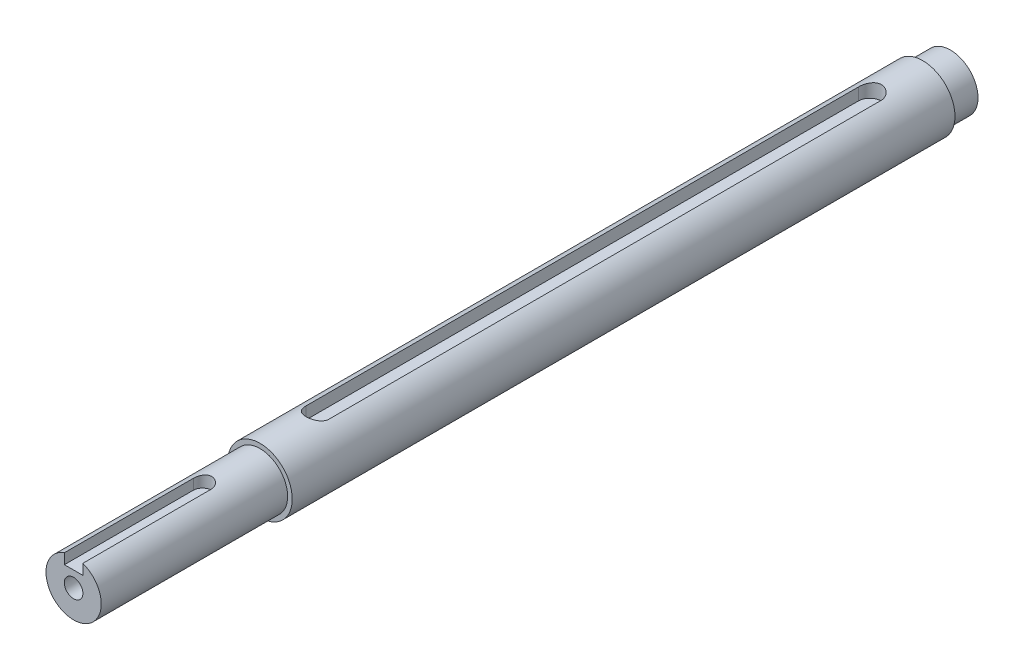
SolidWorks part; units mm, degrees
ref_plane "Front Plane" through (0, 0, 0) normal (0, 0, 1) x (1, 0, 0)
ref_plane "Top Plane" through (0, 0, 0) normal (0, 1, 0) x (1, 0, 0)
ref_plane "Right Plane" through (0, 0, 0) normal (1, 0, 0) x (0, 0, -1)
sketch "Sketch1" plane through (0, 0, 0) normal (1, 0, 0) x (0, 0, -1)
  line L0 (0, 0) -> (183, 0) construction
  line L1 (183, 0) -> (183, 6)
  line L3 (-7.5, 6) -> (-7.5, 0)
  line L5 (-7.5, 6) -> (33, 6)
  line L6 (33, 6) -> (33, 7)
  line L7 (33, 7) -> (177, 7)
  line L8 (-8, 5.9618) -> (-8, -6) construction
  line L9 (33, -12) -> (33, 12) construction
  line L10 (33, -50) -> (33, 50) construction
  line L11 (177, 7) -> (177, 6)
  line L12 (177, 6) -> (183, 6)
  line L13 (183, 0) -> (-7.5, 0)
  dimension "D1" = 12
  dimension "D2" = 0.5
  dimension "D3" = 14
  dimension "D4" = 150
  dimension "D5" = 12
  dimension "D6" = 6
revolve "Revolve1" add sketch "Sketch1" angle 360 about L0
sketch "Sketch2" plane through (0, 0, 7.5) normal (0, 0, 1) x (1, 0, 0)
  circle A0 centre (0, 0) radius 2.0193
  dimension "D1" = 4.0386
extrude "Cut-Extrude1" cut sketch "Sketch2" against normal blind 25
sketch "Sketch3" plane through (0, 0, -183) normal (0, 0, -1) x (-1, 0, 0)
  line L1 (-2.5, 8.9) -> (2.5, 8.9)
  line L2 (-2.5, 8.9) -> (-2.5, 3.9)
  line L3 (-2.5, 3.9) -> (2.5, 3.9)
  line L4 (2.5, 8.9) -> (2.5, 3.9)
  circle A1 centre (0, 0) radius 7 construction
  point P4 (0, 3.9)
  dimension "D1" = 5
  dimension "D2" = 3.1
extrude "Cut-Extrude2" cut sketch "Sketch3" against normal offset from surface (125 mm away) 10 from offset 15 contours L1 L4 L3 L2 up to face at (6, 0, -33) offset against normal yes
sketch "Sketch4" plane through (0, 0, 7.5) normal (0, 0, 1) x (1, 0, 0)
  line L1 (-2, 3.4) -> (2, 3.4)
  line L2 (-2, 3.4) -> (-2, 7.4)
  line L3 (-2, 7.4) -> (2, 7.4)
  line L4 (2, 3.4) -> (2, 7.4)
  line L5 (-2, 3.4) -> (2, 7.4) construction
  line L6 (-2, 7.4) -> (2, 3.4) construction
  circle A2 centre (0, 0) radius 6 construction
  point P0 (0, 5.4)
  dimension "D1" = 4
  dimension "D2" = 2.6
extrude "Cut-Extrude3" cut sketch "Sketch4" against normal blind 30
fillet "Fillet1" 2 edges at (-2, 4.5284, -22.5) (2, 4.5284, -22.5) type full round first side face at (-2, 4.5284, -7.5) second side face at (2, 4.5284, -7.5) middle face at (0, 4.6142, -22.5)
fillet "Fillet2" 2 edges at (-2.5, 5.2192, -43) (2.5, 5.2192, -43) type full round first side face at (-2.5, 5.2192, -105.5) second side face at (2.5, 5.2192, -105.5) middle face at (0, 5.3346, -43)
fillet "Fillet3" 2 edges at (-2.5, 5.2192, -168) (2.5, 5.2192, -168) type full round first side face at (-2.5, 5.2192, -106.75) second side face at (2.5, 5.2192, -106.75) middle face at (0, 5.3346, -168)
